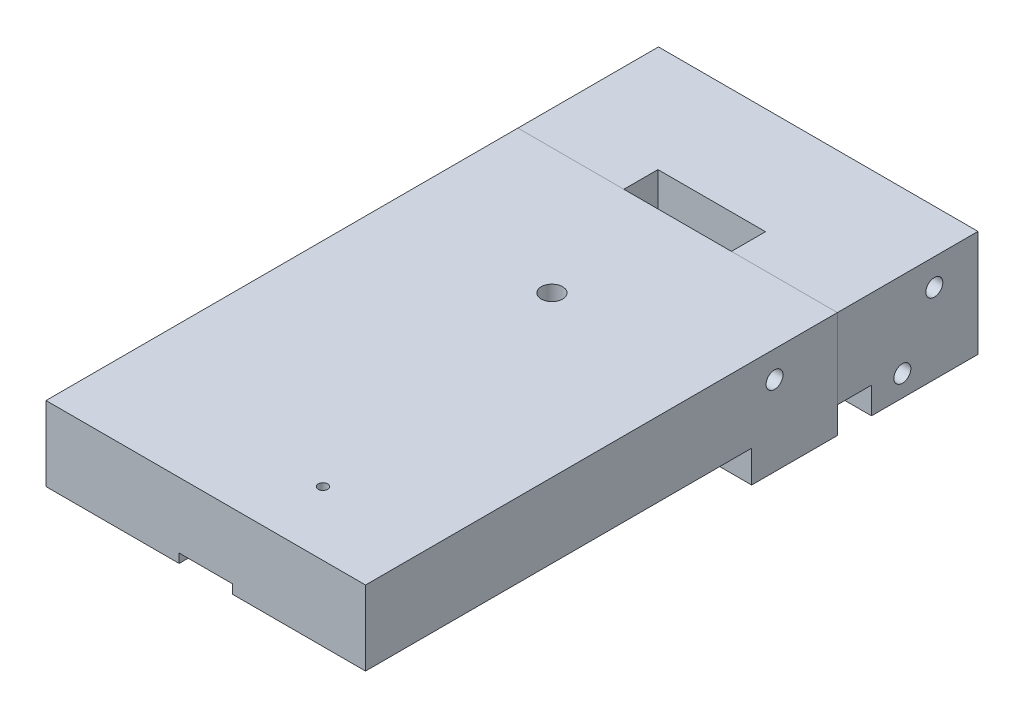
SolidWorks part; units mm, degrees
material "Nylon 6/10"
ref_plane "Front Plane" through (0, 0, 0) normal (0, 0, 1) x (1, 0, 0)
ref_plane "Top Plane" through (0, 0, 0) normal (0, 1, 0) x (1, 0, 0)
ref_plane "Right Plane" through (0, 0, 0) normal (1, 0, 0) x (0, 0, -1)
sketch "Sketch1" plane through (0, 0, 0) normal (0, 1, 0) x (1, 0, 0)
  line L1 (-38.1, -73.025) -> (38.1, -73.025)
  line L2 (-38.1, -73.025) -> (-38.1, 73.025)
  line L3 (-38.1, 73.025) -> (38.1, 73.025)
  line L4 (38.1, -73.025) -> (38.1, 73.025)
  line L5 (-38.1, -73.025) -> (38.1, 73.025) construction
  line L6 (-38.1, 73.025) -> (38.1, -73.025) construction
  point P0 (0, 0)
  dimension "D1" = 76.2
  dimension "D2" = 146.05
extrude "Boss-Extrude1" add sketch "Sketch1" along normal blind 12.7 and the other way blind 12.7
sketch "Sketch2" plane through (0, 0, -73.025) normal (0, 0, -1) x (-1, 0, 0)
  line L1 (-38.1, -12.7) -> (38.1, -12.7) construction
  circle A0 centre (0, -12.7) radius 4.7625
  dimension "D1" = 9.525
extrude "Cut-Extrude1" cut sketch "Sketch2" against normal blind 25.4
ref_plane "Plane1" through (0, -12.7, 0) normal (0, -1, 0) x (-1, 0, 0)
sketch "Sketch3" plane through (0, -12.7, 0) normal (0, -1, 0) x (-1, 0, 0)
  line L0 (10.922, 19.05) -> (38.1, 19.05)
  line L1 (-31.75, -19.05) -> (31.75, -19.05)
  line L2 (-38.1, -73.025) -> (-38.1, 73.025) construction
  line L3 (0, 0) -> (0, 102.0916) construction
  line L5 (-10.922, 19.05) -> (-10.922, 39.497)
  line L6 (31.75, -19.05) -> (38.1, -19.05)
  line L7 (-10.922, 39.497) -> (10.922, 39.497)
  line L8 (10.922, 19.05) -> (10.922, 39.497)
  line L10 (-38.1, -19.05) -> (-31.75, -19.05)
  line L11 (-38.1, -19.05) -> (-38.1, 19.05)
  line L12 (-38.1, 19.05) -> (-10.922, 19.05)
  line L13 (38.1, -19.05) -> (38.1, 19.05)
  line L14 (4.7625, 73.025) -> (4.7625, 47.625)
  line L15 (4.7625, 47.625) -> (-4.7625, 47.625)
  line L16 (-4.7625, 47.625) -> (-4.7625, 73.025)
  line L17 (-4.7625, 73.025) -> (-38.1, 73.025)
  line L18 (-38.1, 73.025) -> (-38.1, -73.025)
  line L19 (-38.1, -73.025) -> (38.1, -73.025)
  line L20 (38.1, -73.025) -> (38.1, 73.025)
  line L21 (38.1, 73.025) -> (4.7625, 73.025)
  line L25 (-4.7625, 73.025) -> (-38.1, 73.025) construction
  line L28 (38.1, -73.025) -> (38.1, 73.025) construction
  line L29 (38.1, 73.025) -> (4.7625, 73.025) construction
  dimension "D6" = 21.844
  dimension "D9" = 20.447
  dimension "D7" = 38.1
  dimension "D10" = 53.975
  dimension "D1" = 0
extrude "Cut-Extrude2" cut sketch "Sketch3" against normal blind 7.62
sketch "Sketch5" plane through (0, 0, 0) normal (0, 1, 0) x (1, 0, 0)
  line L0 (-4.7625, 73.025) -> (-38.1, 73.025) construction
  line L1 (12.827, 47.625) -> (-12.827, 47.625)
  line L2 (12.827, 39.497) -> (12.827, 47.625)
  line L3 (12.827, 39.497) -> (-12.827, 39.497)
  line L4 (0, 0) -> (0, 121.8983) construction
  line L6 (-12.827, 39.497) -> (-12.827, 47.625)
  point P17 (12.827, 39.497)
  point P20 (12.827, 47.625)
  dimension "D1" = 8.128
  dimension "D2" = 25.654
  dimension "D4" = 25.4
extrude "Cut-Extrude4" cut sketch "Sketch5" along normal through all and the other way through all
hole_wizard "1/4-20 Tapped Hole1" positions "Sketch8" profile "Sketch7" tap size "1/4-20" standard "ANSI Inch"
sketch "Sketch8" plane through (-11.0345, 12.7, 14.5475) normal (0, -1, 0) x (-1, 0, 0)
  line L1 (-23.8615, 62.1725) -> (1.7925, 62.1725) construction
  point P0 (-11.0345, 24.0725)
  dimension "D1" = 38.1
  dimension "D2" = 0
sketch "Sketch7" plane through (0, 12.7, -9.525) normal (1, 0, 0) x (0, 0, 1)
  line L0 (0, 0) -> (0, 20.5838)
  line L1 (0, 20.5838) -> (2.5527, 19.05)
  line L2 (2.5527, 19.05) -> (2.5527, 0)
  line L5 (2.5527, 0) -> (0, 0)
  line L10 (0, 20.5838) -> (-2.5527, 19.05) construction
  line L11 (0, -6.35) -> (0, 107.95) construction
  dimension "Tap Drill Dia." = 5.1054
  dimension "Tap Drill Depth" = 19.05
  dimension "Drill Angle" = 118
cosmetic thread "Hole Thread2" parameters "D1"=9.525, "D2"=6.35
sketch "Sketch9" plane through (0, -12.7, 0) normal (0, -1, 0) x (-1, 0, 0)
  line L0 (38.1, -28.575) -> (25.4, -28.575) construction
  line L1 (38.1, -19.05) -> (38.1, -73.025) construction
  line L3 (-38.1, -19.05) -> (38.1, -19.05) construction
  line L4 (38.1, 28.575) -> (25.4, 28.575) construction
  line L5 (38.1, 73.025) -> (38.1, 19.05) construction
  line L6 (-10.922, 19.05) -> (-38.1, 19.05) construction
  line L7 (0, 0) -> (0, 53.9724) construction
  circle A0 centre (31.75, 28.575) radius 1.5964
  circle A1 centre (31.75, -28.575) radius 1.5964
  circle A2 centre (-31.75, -28.575) radius 1.5964
  circle A3 centre (-31.75, 28.575) radius 1.5964
  dimension "D1" = 9.525
  dimension "D2" = 3.1928
  dimension "D3" = 9.525
extrude "8-32 Tapped Hole" cut sketch "Sketch9" against normal blind 12.7
ref_plane "Plane2" through (0, 0, -19.05) normal (0, 0, 1) x (1, 0, 0)
ref_plane "Plane3" through (0, -5.08, 0) normal (0, -1, 0) x (-1, 0, 0)
sketch "Sketch11" plane through (0, -5.08, 0) normal (0, -1, 0) x (-1, 0, 0)
  line L0 (38.1, -73.025) -> (-38.1, -73.025) construction
  line L2 (0.0025, -28.575) -> (-0.0025, -28.575)
  line L3 (6.35, -34.9225) -> (6.35, -73.025)
  line L4 (6.35, -73.025) -> (-6.35, -73.025)
  line L5 (-6.35, -34.9225) -> (-6.35, -73.025)
  line L6 (6.35, -28.575) -> (-6.35, -73.025) construction
  line L7 (6.35, -73.025) -> (-6.35, -28.575) construction
  line L8 (0, -50.8) -> (0, -73.025) construction
  arc A0 (-0.0025, -28.575) -> (-6.35, -34.9225) centre (-0.0025, -34.9225) ccw
  arc A1 (0.0025, -28.575) -> (6.35, -34.9225) centre (0.0025, -34.9225) cw
  point P0 (0, -50.8)
  dimension "D2" = 6.3475
  dimension "D1" = 12.7
  dimension "D3" = 44.45
extrude "Cut-Extrude7" cut sketch "Sketch11" against normal blind 2.159 and the other way through all
sketch "Sketch12" plane through (0, -5.08, 0) normal (0, -1, 0) x (1, 0, 0)
  line L0 (0, 0) -> (0, 79.2462) construction
  line L2 (6.35, 73.025) -> (-6.35, 73.025) construction
  circle A0 centre (12.7, 66.675) radius 2.0193
  circle A1 centre (-12.7, 66.675) radius 2.0193
  dimension "D1" = 4.0386
  dimension "D2" = 25.4
  dimension "D3" = 6.35
extrude "Cut-Extrude8" cut sketch "Sketch12" against normal blind 12.7 and the other way through all
sketch "Sketch13" plane through (0, -12.7, 0) normal (0, -1, 0) x (1, 0, 0)
  line L0 (38.1, -19.05) -> (38.1, -73.025) construction
  line L1 (12.827, -39.497) -> (38.1, -39.497)
  line L2 (12.827, -39.497) -> (12.827, -47.625)
  line L3 (12.827, -47.625) -> (38.1, -47.625)
  line L4 (38.1, -39.497) -> (38.1, -47.625)
  line L5 (12.827, -47.625) -> (4.7625, -47.625) construction
extrude "Cut-Extrude9" cut sketch "Sketch13" against normal blind 6.35
ref_plane "Plane4" through (0, 0, -39.497) normal (0, 0, -1) x (-1, 0, 0)
sketch "Sketch15" plane through (0, 0, -73.025) normal (0, 0, -1) x (-1, 0, 0)
  line L0 (-38.1, 0) -> (38.1, 0) construction
  line L1 (-38.1, -12.7) -> (-38.1, 12.7) construction
  line L2 (38.1, -12.7) -> (38.1, 12.7) construction
  circle A0 centre (-24.13, 0) radius 2.0193
  circle A1 centre (24.13, 0) radius 2.0193
  dimension "D1" = 4.0386
  dimension "D3" = 13.97
  dimension "D2" = 13.97
extrude "Cut-Extrude11" cut sketch "Sketch15" against normal blind 57.15
sketch "Sketch17" plane through (0, 0, -73.025) normal (0, 0, -1) x (-1, 0, 0)
  line L0 (-38.1, 0) -> (38.1, 0) construction
  line L3 (38.1, -12.7) -> (38.1, 12.7) construction
  circle A0 centre (-24.13, 0) radius 4.2164
  circle A1 centre (24.13, 0) radius 4.2164
  circle A3 centre (24.13, 0) radius 2.0193 construction
  circle A4 centre (-24.13, 0) radius 2.0193 construction
  dimension "D1" = 8.4328
extrude "Cut-Extrude12" cut sketch "Sketch17" against normal blind 5.461
sketch "Sketch19" plane through (0, -12.7, 0) normal (0, -1, 0) x (1, 0, 0)
  line L1 (-4.7625, -73.025) -> (-38.1, -73.025) construction
  line L2 (-38.1, -73.025) -> (-38.1, -19.05) construction
  circle A0 centre (-31.75, -57.15) radius 2.0193
  circle A1 centre (12.7, -57.15) radius 2.0193
  dimension "D1" = 4.0386
  dimension "D2" = 15.875
  dimension "D3" = 6.35
  dimension "D4" = 44.45
extrude "Cut-Extrude14" cut sketch "Sketch19" against normal blind 12.7
sketch "Sketch22" plane through (0, -12.7, 0) normal (0, -1, 0) x (1, 0, 0)
  line L0 (-12.7, -32.0675) -> (12.7, -32.0675) construction
  line L1 (-12.7, -21.3995) -> (12.7, -21.3995) construction
  line L2 (-12.7, -32.8612) -> (12.7, -32.8612)
  line L3 (-12.7, -31.2737) -> (12.7, -31.2737)
  line L4 (-12.7, -20.6058) -> (12.7, -20.6058)
  line L5 (-12.7, -22.1932) -> (12.7, -22.1932)
  line L6 (0, -39.4682) -> (0, -19.7785) construction
  line L7 (10.922, -26.7335) -> (-10.922, -26.7335) construction
  line L8 (10.922, -39.497) -> (10.922, -19.05) construction
  line L9 (-10.922, -19.05) -> (-10.922, -39.497) construction
  arc A0 (-12.7, -20.6058) -> (-12.7, -22.1932) centre (-12.7, -21.3995) ccw
  arc A1 (12.7, -22.1932) -> (12.7, -20.6058) centre (12.7, -21.3995) ccw
  arc A2 (-12.7, -32.8612) -> (-12.7, -31.2737) centre (-12.7, -32.0675) cw
  arc A3 (12.7, -31.2737) -> (12.7, -32.8612) centre (12.7, -32.0675) cw
  point P6 (0, -21.3995)
  point P12 (10.922, -29.2735)
  point P17 (0, -32.0675)
  dimension "D1" = 1.5875
  dimension "D2" = 25.4
  dimension "D3" = 10.668
  dimension "D4" = 2.54
extrude "Cut-Extrude16" cut sketch "Sketch22" against normal blind 2.286
sketch "Sketch23" plane through (0, -12.7, 0) normal (0, -1, 0) x (1, 0, 0)
  line L1 (-10.922, -39.497) -> (10.922, -39.497)
  line L2 (-10.922, -39.497) -> (-10.922, -22.225)
  line L3 (-7.747, -19.05) -> (7.747, -19.05)
  line L4 (10.922, -39.497) -> (10.922, -22.225)
  arc A0 (-7.747, -19.05) -> (-10.922, -22.225) centre (-7.747, -22.225) ccw
  arc A1 (7.747, -19.05) -> (10.922, -22.225) centre (7.747, -22.225) cw
  point P9 (10.922, -19.05)
  dimension "D1" = 3.175
extrude "Cut-Extrude18" cut sketch "Sketch23" against normal blind 11.176
sketch "Sketch25" plane through (38.1, 0, 0) normal (1, 0, 0) x (0, 0, -1)
  line L0 (-73.025, 12.7) -> (73.025, 12.7) construction
  line L1 (73.025, -12.7) -> (73.025, 12.7) construction
  point P0 (62.611, 6.35)
  point P1 (54.991, -7.62)
  point P2 (24.511, 6.35)
  dimension "D1" = 7.62
  dimension "D2" = 13.97
  dimension "D3" = 38.1
  dimension "D4" = 6.35
  dimension "D5" = 10.414
hole_wizard "#10-32 Tapped Hole1" positions "Sketch29" profile "Sketch28" tap size "#10-32" standard "ANSI Inch"
sketch "Sketch29" plane through (38.1, 0, 0) normal (1, 0, 0) x (0, 0, -1)
  point P0 (62.611, 6.35)
  point P3 (54.991, -7.62)
  point P6 (24.511, 6.35)
sketch "Sketch28" plane through (38.1, 6.35, -62.611) normal (0, 1, 0) x (0, 0, -1)
  line L0 (0, 0) -> (0, 15.3357)
  line L1 (0, 15.3357) -> (2.0193, 14.1224)
  line L2 (2.0193, 14.1224) -> (2.0193, 0)
  line L5 (2.0193, 0) -> (0, 0)
  line L10 (0, 15.3357) -> (-2.0193, 14.1224) construction
  line L11 (0, -6.35) -> (0, 107.95) construction
  dimension "Tap Drill Dia." = 4.0386
  dimension "Tap Drill Depth" = 14.1224
  dimension "Drill Angle" = 118
cosmetic thread "Hole Thread3" parameters "D1"=10.16, "D2"=4.826
cosmetic thread "Hole Thread4" parameters "D1"=10.16, "D2"=4.826
cosmetic thread "Hole Thread5" parameters "D1"=10.16, "D2"=4.826
sketch "Sketch30" plane through (0, -12.7, 0) normal (0, -1, 0) x (1, 0, 0)
  circle A0 centre (12.7, 57.785) radius 3.8897
  circle A1 centre (0, -9.525) radius 2.5527 construction
  dimension "D2" = 12.7
  dimension "D1" = 67.31
sketch "Sketch31" plane through (0, -12.7, 0) normal (0, -1, 0) x (1, 0, 0)
  line L0 (38.1, 19.05) -> (-38.1, 19.05) construction
  line L1 (-38.1, 73.025) -> (38.1, 73.025)
  line L2 (-38.1, 73.025) -> (-38.1, 19.05)
  line L3 (-38.1, 19.05) -> (38.1, 19.05)
  line L4 (38.1, 73.025) -> (38.1, 19.05)
  line L6 (38.1, 73.025) -> (38.1, -73.025) construction
extrude "Cut-Extrude20" cut sketch "Sketch31" against normal up to surface (7.62 mm away) up to face at (0, -5.08, -6.9723)
hole_wizard "#4-40 Tapped Hole1" positions "3DSketch1" profile "Sketch32" tap size "#4-40" standard "ANSI Inch" end condition through all
sketch3d "3DSketch1"
  point P0 (12.7, -5.08, 57.785)
sketch "Sketch32" plane through (12.7, -5.08, 57.785) normal (1, 0, 0) x (0, 0, -1)
  line L0 (0, 0) -> (0, 17.78)
  line L1 (0, 17.78) -> (1.1303, 17.78)
  line L2 (1.1303, 17.78) -> (1.1303, 0)
  line L5 (1.1303, 0) -> (0, 0)
  line L11 (0, -6.35) -> (0, 107.95) construction
  dimension "Thru Tap Drill Dia." = 2.2606
  dimension "Thru Tap Drill Depth" = 17.78
cosmetic thread "Hole Thread6" parameters "D2"=2.8448
hole_wizard "#8-32 Tapped Hole1" positions "Sketch35" profile "Sketch34" tap size "#8-32" standard "ANSI Inch"
sketch "Sketch35" plane through (0, -12.7, 0) normal (0, -1, 0) x (-1, 0, 0)
  line L0 (-38.1, 73.025) -> (-4.7625, 73.025) construction
  line L4 (0, 0) -> (0, 118.5831) construction
  point P0 (-12.7, 68.2625)
  point P2 (12.7, 68.2625)
  dimension "D1" = 25.4
  dimension "D2" = 4.7625
sketch "Sketch34" plane through (12.7, -12.7, -68.2625) normal (1, 0, 0) x (0, 0, -1)
  line L0 (0, 0) -> (0, 13.7378)
  line L1 (0, 13.7378) -> (1.7272, 12.7)
  line L2 (1.7272, 12.7) -> (1.7272, 0)
  line L5 (1.7272, 0) -> (0, 0)
  line L10 (0, 13.7378) -> (-1.7272, 12.7) construction
  line L11 (0, -6.35) -> (0, 107.95) construction
  dimension "Tap Drill Dia." = 3.4544
  dimension "Tap Drill Depth" = 12.7
  dimension "Drill Angle" = 118
cosmetic thread "Hole Thread7" parameters "D1"=10.795, "D2"=4.1656
cosmetic thread "Hole Thread8" parameters "D1"=10.795, "D2"=4.1656
split "Split1" trim tools "Plane4" bodies to split 131 resulting bodies 124 125
